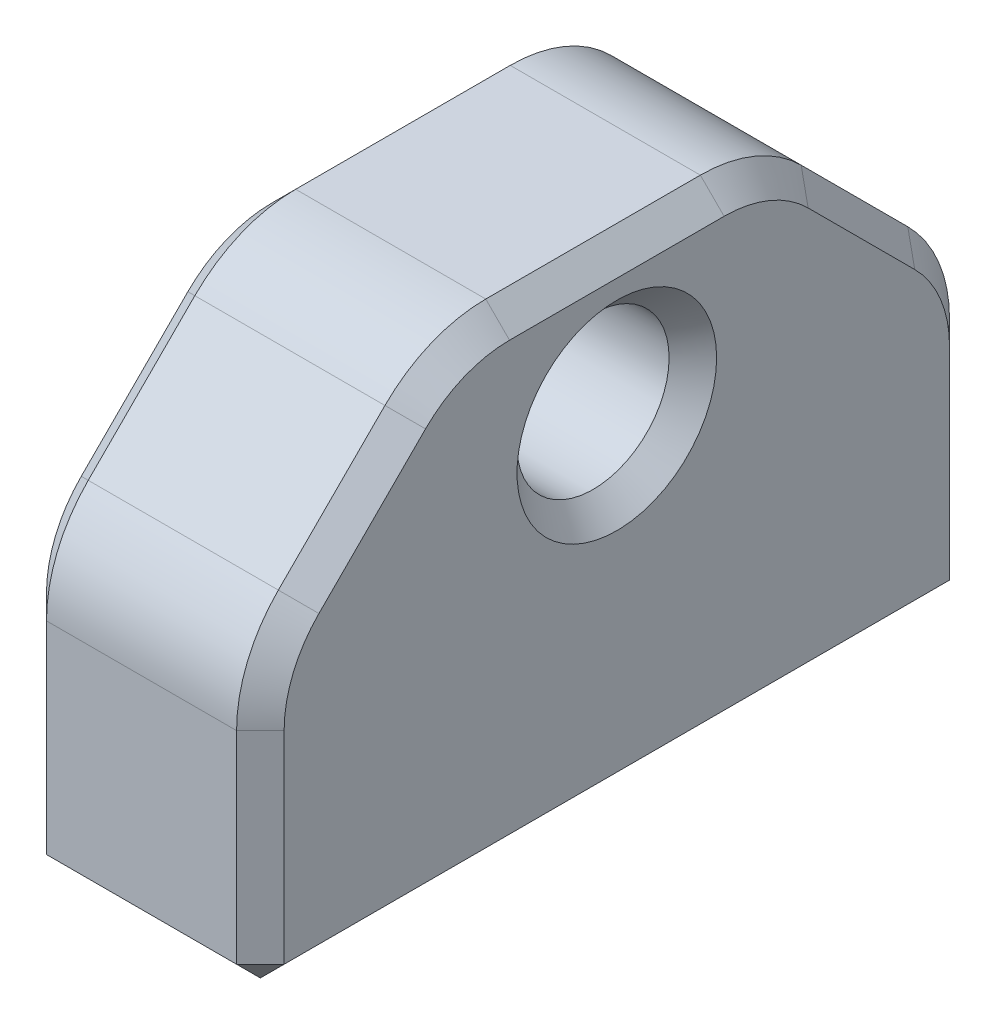
SolidWorks part; units mm, degrees
ref_plane "Front Plane" through (0, 0, 0) normal (0, 0, 1) x (1, 0, 0)
ref_plane "Top Plane" through (0, 0, 0) normal (0, 1, 0) x (1, 0, 0)
ref_plane "Right Plane" through (0, 0, 0) normal (1, 0, 0) x (0, 0, -1)
sketch "Sketch1" plane through (0, 0, 0) normal (0, 1, 0) x (1, 0, 0)
  line L0 (0, 6.35) -> (0, -6.35) construction
  line L1 (-3.175, 9.525) -> (3.175, 9.525)
  line L2 (-3.175, 9.525) -> (-3.175, -9.525)
  line L3 (-3.175, -9.525) -> (3.175, -9.525)
  line L4 (3.175, 9.525) -> (3.175, -9.525)
  line L5 (-3.175, 9.525) -> (3.175, -9.525) construction
  line L6 (-3.175, -9.525) -> (3.175, 9.525) construction
  circle A0 centre (0, 6.35) radius 2.032
  circle A1 centre (0, -6.35) radius 2.032
  point P0 (0, 0)
  point P9 (0, 0)
  dimension "D3" = 4.064
  dimension "D1" = 19.05
  dimension "D2" = 6.35
  dimension "D4" = 12.7
extrude "Boss-Extrude1" add sketch "Sketch1" along normal blind 12.7 contours L2 L3 L4 L1
sketch "Sketch2" plane through (-3.175, 0, 0) normal (-1, 0, 0) x (0, 0, 1)
  line L0 (0, 12.7) -> (0, 8.89)
  line L1 (-9.525, 12.7) -> (9.525, 12.7) construction
  circle A0 centre (0, 8.89) radius 2.032
  dimension "D1" = 4.064
  dimension "D2" = 3.81
extrude "Cut-Extrude1" cut sketch "Sketch2" against normal through all contours A0
extrude "Cut-Extrude2" cut sketch "Sketch1<3>" along normal blind 7.62 contours A0 | A1
sketch "Sketch1<3>" plane through (0, 0, 0) normal (0, 1, 0) x (1, 0, 0) same geometry as "Sketch1"
chamfer "Chamfer1" distance 5.08 angle 45 2 edges at (0, 12.7, 9.525) (0, 12.7, -9.525)
fillet "Fillet1" radius 3.81 4 edges at (0, 7.62, 9.525) (0, 12.7, 4.445) (0, 7.62, -9.525) (0, 12.7, -4.445)
chamfer "Chamfer2" distance 0.635 angle 45 26 edges at (3.175, 8.89, 2.032) (0, 0, 9.525) (3.175, 12.41, 4.3249) (3.175, 12.7, 0) (3.175, 12.41, -4.3249) (3.175, 10.16, -6.985) (3.175, 7.4999, -9.235) (3.175, 3.0209, -9.525) (3.175, 10.16, 6.985) (3.175, 7.4999, 9.235) (3.175, 3.0209, 9.525) (3.175, 0, 0) (0, 0, -9.525) (-3.175, 0, 0) (-3.175, 3.0209, -9.525) (-3.175, 7.4999, -9.235) (-3.175, 10.16, -6.985) (-3.175, 12.41, -4.3249) (-3.175, 12.7, 0) (-3.175, 12.41, 4.3249) (-3.175, 10.16, 6.985) (-3.175, 7.4999, 9.235) (-3.175, 3.0209, 9.525) (-3.175, 8.89, 2.032) (0, 0, 8.382) (0, 0, -4.318)
